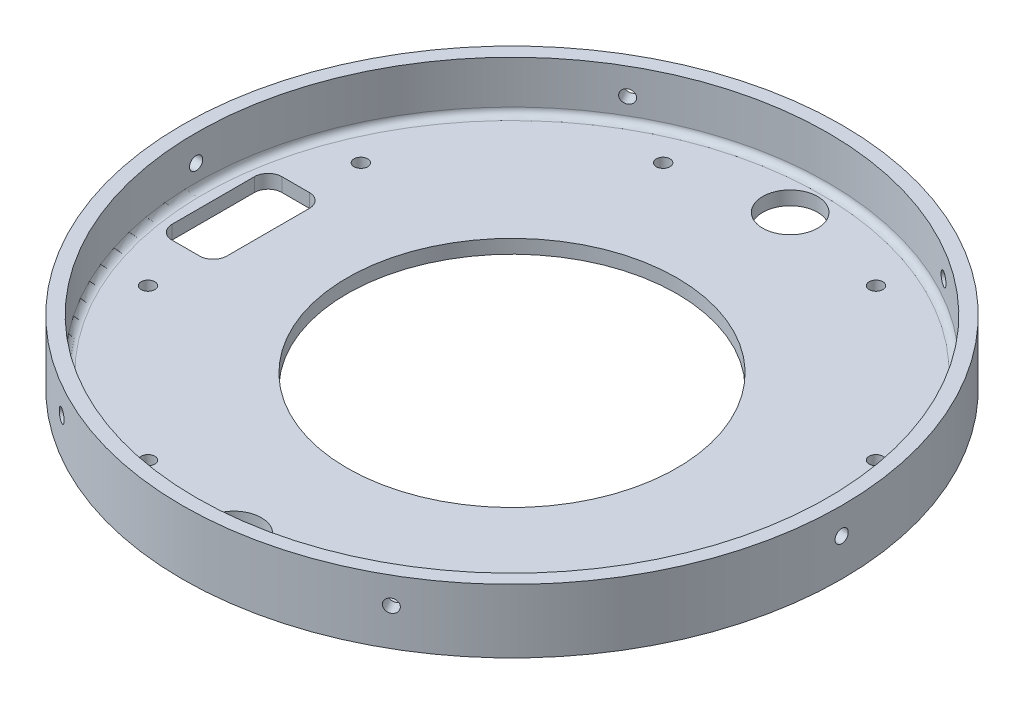
SolidWorks part; units mm, degrees
material "6061-T6 (SS)"
ref_plane "Front Plane" through (0, 0, 0) normal (0, 0, 1) x (1, 0, 0)
ref_plane "Top Plane" through (0, 0, 0) normal (0, 1, 0) x (1, 0, 0)
ref_plane "Right Plane" through (0, 0, 0) normal (1, 0, 0) x (0, 0, -1)
sketch "Sketch1" plane through (0, 0, 0) normal (0, 1, 0) x (1, 0, 0)
  circle A0 centre (0, 0) radius 76.2
extrude "Boss-Extrude1" add sketch "Sketch1" along normal blind 16.256
shell "Shell1" thickness 3.175 removed face at (0, 16.256, 76.2)
fillet "Fillet1" radius 1.5875 1 edges at (0, 3.175, 73.025)
sketch "Sketch2" plane through (0, 0, 0) normal (0, -1, 0) x (1, 0, 0)
  circle A0 centre (0, 0) radius 38.1
  dimension "D1" = 76.2
extrude "Cut-Extrude1" cut sketch "Sketch2" against normal blind 16.256
sketch "Sketch3" plane through (0, 0, 0) normal (1, 0, 0) x (0, 0, -1)
  line L0 (0, 0) -> (0, 8.636) construction
  circle A0 centre (0, 8.636) radius 1.524
  dimension "D2" = 3.048
  dimension "D1" = 8.636
extrude "Cut-Extrude2" cut sketch "Sketch3" against normal blind 76.2
pattern_circular "CirPattern1" count 6 over 360 about axis through (0, 16.256, 0) along (0, -1, 0) of "Cut-Extrude2"
sketch "Sketch5" plane through (0, 16.256, 0) normal (0, 1, 0) x (1, 0, 0)
  circle A0 centre (0, 0) radius 76.2
extrude "Cut-Extrude4" cut sketch "Sketch5" against normal blind 1.524
sketch "Sketch6" plane through (0, 3.175, 0) normal (0, 1, 0) x (1, 0, 0)
  line L0 (0, 0) -> (0, 71.4375) construction
  line L1 (0, 0) -> (61.8667, 35.7187) construction
  line L2 (0, 0) -> (61.8667, -35.7188) construction
  line L3 (0, 0) -> (0, -71.4375) construction
  line L4 (0, 0) -> (-61.8667, -35.7187) construction
  line L5 (0, 0) -> (-61.8667, 35.7188) construction
  circle A0 centre (0, 0) radius 71.4375 construction
  circle A1 centre (0, 0) radius 73.025 construction
  circle A2 centre (0, 64.2874) radius 6.35
  circle A3 centre (0, -64.2874) radius 6.35
  point P15 (0, 0)
  dimension "D2" = 64.2874
  dimension "D4" = 12.7
  dimension "D5" = 12.7
  dimension "D3" = 64.2874
  dimension "D1" = 6
extrude "Cut-Extrude5" cut sketch "Sketch6" against normal blind 12.7
sketch "Sketch7" plane through (0, 3.175, 0) normal (0, 1, 0) x (1, 0, 0)
  line L0 (0, 0) -> (0, 59.525) construction
  line L1 (24.6, 59.525) -> (-24.6, 59.525) construction
  line L2 (0, 0) -> (-76.2, 0) construction
  line L3 (24.6, -59.525) -> (-24.6, -59.525) construction
  line L4 (0, 0) -> (0, -59.525) construction
  line L5 (0, 0) -> (53.8815, 53.8815) construction
  line L6 (-59.525, 24.6) -> (-59.525, -24.6) construction
  line L7 (59.525, 24.6) -> (59.525, -24.6) construction
  line L8 (-59.525, 0) -> (59.525, 0) construction
  circle A0 centre (-24.6, 59.525) radius 1.5875
  circle A1 centre (24.6, 59.525) radius 1.5875
  circle A2 centre (0, 0) radius 76.2 construction
  circle A3 centre (24.6, -59.525) radius 1.5875
  circle A4 centre (-24.6, -59.525) radius 1.5875
  circle A5 centre (-59.525, -24.6) radius 1.5875
  circle A6 centre (-59.525, 24.6) radius 1.5875
  circle A7 centre (59.525, 24.6) radius 1.5875
  circle A8 centre (59.525, -24.6) radius 1.5875
  dimension "D1" = 3.175
  dimension "D2" = 24.6
  dimension "D3" = 59.525
extrude "Cut-Extrude6" cut sketch "Sketch7" against normal blind 6.35
sketch "Sketch8" plane through (0, 3.175, 0) normal (0, 1, 0) x (1, 0, 0)
  line L0 (0, 0) -> (-76.2, 0) construction
  line L2 (-69.05, -12.7) -> (-56.35, -12.7)
  line L3 (-69.05, -12.7) -> (-69.05, 12.7)
  line L4 (-69.05, 12.7) -> (-56.35, 12.7)
  line L5 (-56.35, -12.7) -> (-56.35, 12.7)
  line L6 (-69.05, -12.7) -> (-56.35, 12.7) construction
  line L7 (-69.05, 12.7) -> (-56.35, -12.7) construction
  circle A0 centre (0, 0) radius 76.2 construction
  point P6 (-62.7, 0)
  dimension "D1" = 69.05
  dimension "D2" = 12.7
  dimension "D3" = 25.4
extrude "Cut-Extrude7" cut sketch "Sketch8" against normal blind 6.35
fillet "Fillet2" radius 3.175 4 edges at (-69.05, 1.5875, 12.7) (-56.35, 1.5875, 12.7) (-56.35, 1.5875, -12.7) (-69.05, 1.5875, -12.7)
